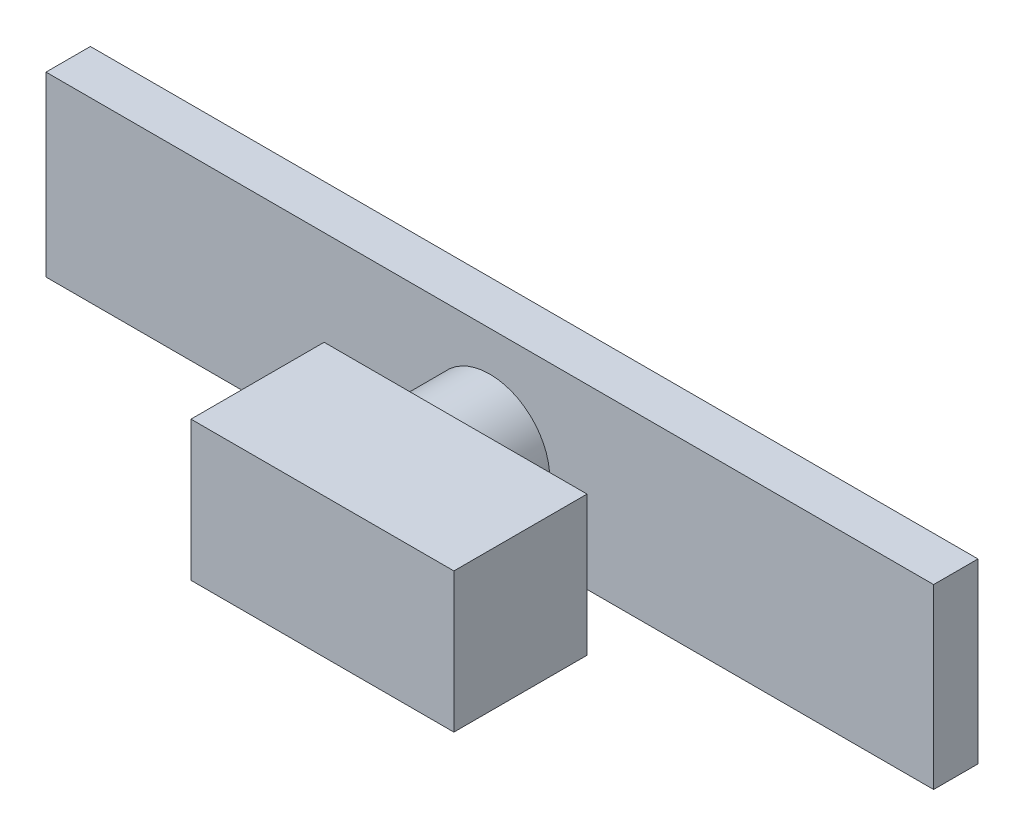
SolidWorks part; units mm, degrees
ref_plane "Front Plane" through (0, 0, 0) normal (0, 0, 1) x (1, 0, 0)
ref_plane "Top Plane" through (0, 0, 0) normal (0, 1, 0) x (1, 0, 0)
ref_plane "Right Plane" through (0, 0, 0) normal (1, 0, 0) x (0, 0, -1)
sketch "Sketch2" plane through (0, 0, 0) normal (0, 0, 1) x (1, 0, 0)
  line L1 (-47.8692, 21.2481) -> (206.1308, 21.2481)
  line L2 (-47.8692, 21.2481) -> (-47.8692, 8.5481)
  line L3 (-47.8692, 8.5481) -> (206.1308, 8.5481)
  line L4 (206.1308, 21.2481) -> (206.1308, 8.5481)
  dimension "D1" = 12.7
  dimension "D2" = 254
extrude "Boss-Extrude1" add sketch "Sketch2" along normal blind 50.8
sketch "Sketch3" plane through (0, 21.2481, 0) normal (0, 1, 0) x (1, 0, 0)
  circle A0 centre (79.1308, -28.4831) radius 17.1408
extrude "Boss-Extrude2" add sketch "Sketch3" along normal blind 19.05
sketch "Sketch4" plane through (0, 40.2981, 0) normal (0, 1, 0) x (1, 0, 0)
  line L1 (50.7675, -8.111) -> (126.0034, -8.111)
  line L2 (50.7675, -8.111) -> (50.7675, -48.0661)
  line L3 (50.7675, -48.0661) -> (126.0034, -48.0661)
  line L4 (126.0034, -8.111) -> (126.0034, -48.0661)
extrude "Boss-Extrude3" add sketch "Sketch4" along normal blind 38.1
scale "Scale2" scale about centroid uniform scaling yes scale factor 0.06
move or copy body "Body-Move/Copy1" bodies to move or copy 105 copy no rotation origin (0, 33.6669, 26.5501) rotation axis (1, 0, 0) rotation angle 90
move or copy body "Body-Move/Copy3" bodies to move or copy 106 copy no translate (-50.8, 0, -50.8)
scale "Scale5" scale about centroid uniform scaling yes scale factor 0.25
move or copy body "Body-Move/Copy5" bodies to move or copy 111 copy no translate (50.8, 0, 0)
